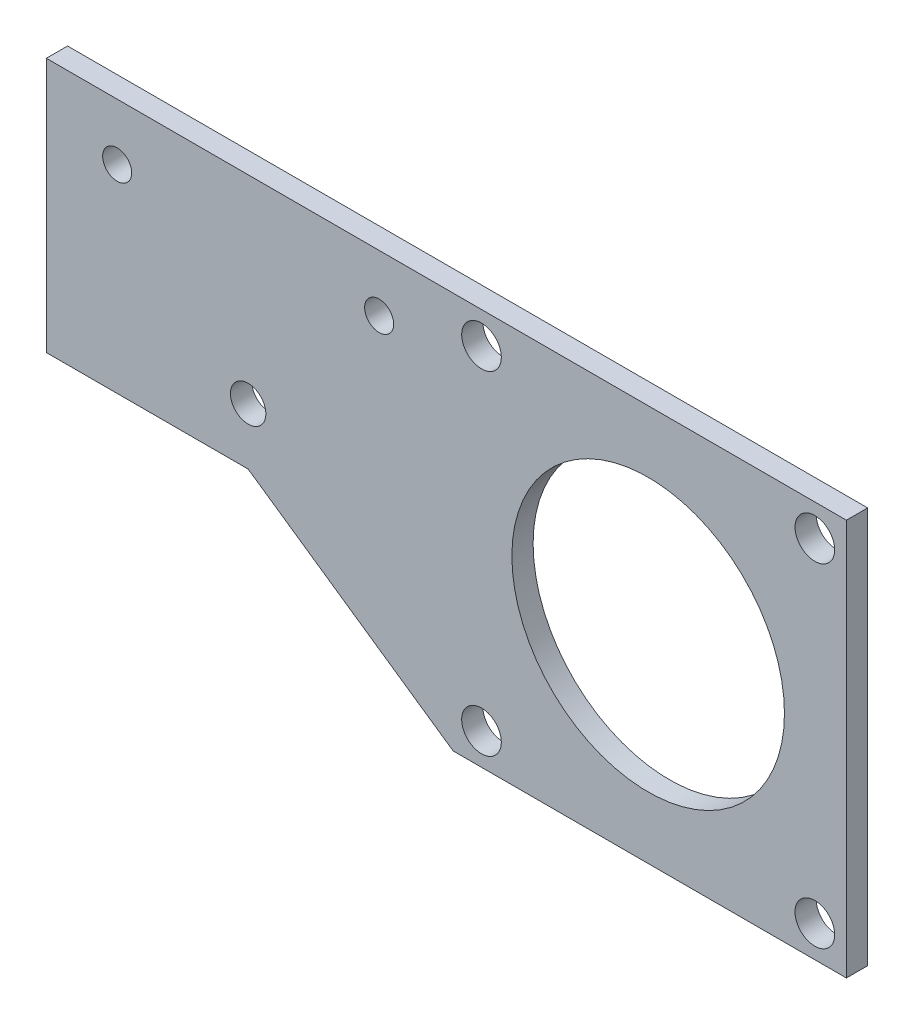
SolidWorks part; units mm, degrees
ref_plane "Front Plane" through (0, 0, 0) normal (0, 0, 1) x (1, 0, 0)
ref_plane "Top Plane" through (0, 0, 0) normal (0, 1, 0) x (1, 0, 0)
ref_plane "Right Plane" through (0, 0, 0) normal (1, 0, 0) x (0, 0, -1)
sketch "Sketch1" plane through (0, 0, 0) normal (0, 0, 1) x (1, 0, 0)
  line L0 (85, 56) -> (85, 0) construction
  line L1 (0, 56) -> (113, 56)
  line L2 (0, 56) -> (0, 0)
  line L3 (0, 0) -> (113, 0)
  line L4 (113, 56) -> (113, 0)
  line L5 (57, 56) -> (57, 0) construction
  line L6 (61.46, -974.9593) -> (61.46, 49025.0407) construction
  line L7 (108.54, -973.2179) -> (108.54, 49026.7821) construction
  line L8 (-925.8289, 51.54) -> (49074.1711, 51.54) construction
  line L9 (-926.3265, 4.46) -> (49073.6735, 4.46) construction
  circle A0 centre (85, 28) radius 19.25
  circle A1 centre (28.5, 28) radius 2.5
  circle A2 centre (61.46, 51.54) radius 2.8
  circle A3 centre (61.46, 4.46) radius 2.8
  circle A4 centre (108.54, 4.46) radius 2.8
  circle A5 centre (108.54, 51.54) radius 2.8
  dimension "D4" = 38.5
  dimension "D5" = 5
  dimension "D12" = 5.6
  dimension "D1" = 113
  dimension "D2" = 56
  dimension "D3" = 28
  dimension "D6" = 56.5
  dimension "D7" = 56
  dimension "D8" = 4.46
  dimension "D9" = 4.46
  dimension "D10" = 4.46
  dimension "D11" = 4.46
extrude "Boss-Extrude1" add sketch "Sketch1" along normal blind 3
sketch "Sketch2" plane through (0, 0, 3) normal (0, 0, 1) x (1, 0, 0)
  line L0 (0, 28) -> (113, 28) construction
  line L1 (0, 56) -> (0, 0) construction
  line L2 (113, 0) -> (113, 56) construction
  line L3 (57.46, 0) -> (28.5, 20)
  line L4 (0, 20) -> (0, 28)
  line L5 (28.5, 20) -> (0, 20)
  line L7 (28.5, 36) -> (28.5, 20) construction
  line L8 (0, 0) -> (113, 0) construction
  line L9 (57.46, 0) -> (11.4799, -13.7322)
  line L10 (11.4799, -13.7322) -> (-30.0355, 6.5289)
  line L11 (-30.0355, 6.5289) -> (0, 28)
  circle A2 centre (61.46, 4.46) radius 2.8 construction
  point P10 (0, 0)
  point P19 (28.5, 28)
  point P23 (20.5, 28)
  dimension "D1" = 4
  dimension "D2" = 8
extrude "Cut-Extrude1" cut sketch "Sketch2" against normal blind 3
sketch "Sketch3" plane through (0, 0, 0) normal (0, 0, -1) x (-1, 0, 0)
  circle A0 centre (-47.0012, 47.9994) radius 2.05
  circle A1 centre (-10.0012, 48.0016) radius 2.05
  circle A2 centre (-10.0012, 48.0016) radius 2.05 construction
  circle A3 centre (-47.0012, 47.9994) radius 2.05 construction
extrude "Cut-Extrude2" cut sketch "Sketch3" against normal blind 10
